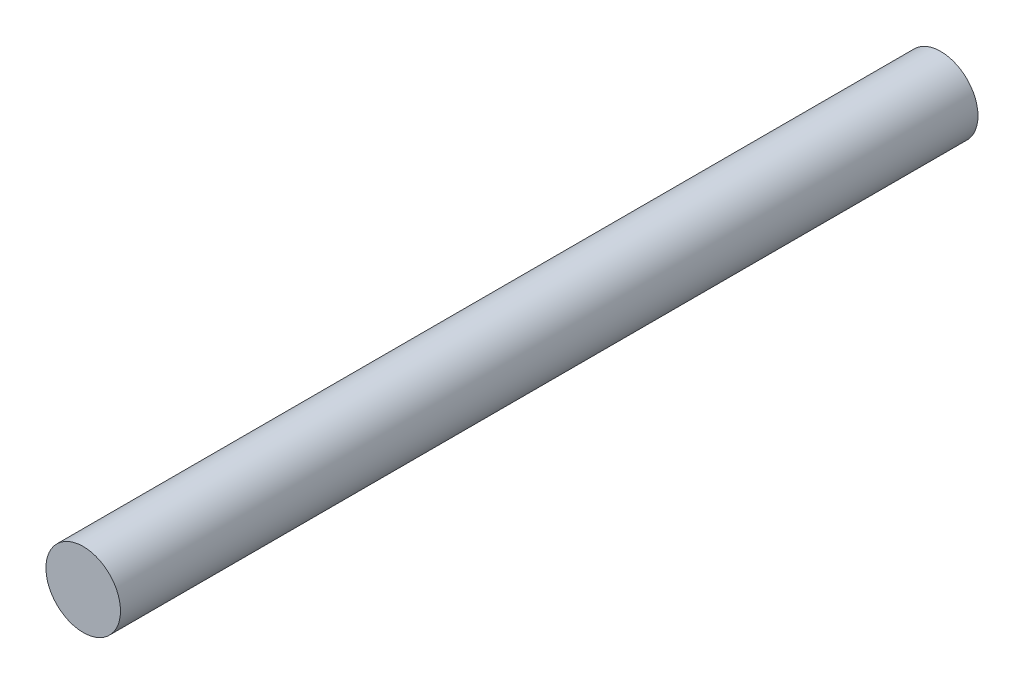
SolidWorks part; units mm, degrees
material "Hexcel AS4C (3000 Filaments)"
ref_plane "Front" through (0, 0, 0) normal (0, 0, 1) x (1, 0, 0)
ref_plane "Top" through (0, 0, 0) normal (0, 1, 0) x (1, 0, 0)
ref_plane "Right" through (0, 0, 0) normal (1, 0, 0) x (0, 0, -1)
sketch "Sketch1" plane through (0, 0, 0) normal (0, 0, 1) x (1, 0, 0)
  circle A0 centre (0, 0) radius 3.175
  dimension "D1" = 6.35
extrude "Boss-Extrude1" add sketch "Sketch1" along normal blind 73.025
equation "\"truss_member_od\" = .25in"
equation "\"truss_member_id\"= 0in"
equation "\"truss_member_L1\" = 2.125in"
equation "\"D1@Sketch1\"=\"truss_member_od\""
equation "\"D1@Boss-Extrude1\"=\"truss_member_L2\""
equation "\"truss_member_L2\" = 2.875in"
equation "\"connector_hole_depth\" = .375in"
